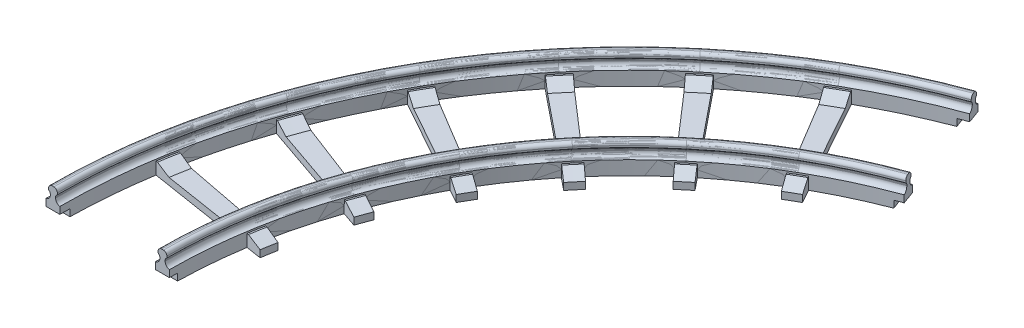
SolidWorks part; units mm, degrees
other "标注1"
sketch "草图3" plane through (-22.25, 4, -10) normal (-0.231, 0.6469, -0.7268) x (-0.9696, -0.2151, 0.1167)
ref_plane "前视基准面" through (0, 0, 0) normal (0, 0, 1) x (1, 0, 0)
ref_plane "上视基准面" through (0, 0, 0) normal (0, 1, 0) x (1, 0, 0)
ref_plane "右视基准面" through (0, 0, 0) normal (1, 0, 0) x (0, 0, -1)
other "Configuration Table"
sketch "草图4" plane through (0, 0, 0) normal (0, 0, 1) x (1, 0, 0)
  line L0 (0, 0) -> (31.5, 0) construction
  line L1 (0.75, -1.5) -> (1.25, -1.5)
  line L3 (0, 0) -> (1.25, 0)
  line L4 (1.25, -1.5) -> (1.25, 0)
  line L5 (0, 0) -> (-1.25, 0)
  line L10 (0.75, -1.5) -> (0.75, -4)
  line L11 (-0.75, -1.5) -> (-1.25, -1.5)
  line L12 (0.75, -4) -> (2, -4)
  line L14 (0, -8) -> (2, -8)
  line L15 (2, -4) -> (2, -8)
  line L16 (-1.25, 0) -> (-1.25, -1.5)
  line L20 (-0.75, -1.5) -> (-0.75, -4)
  line L21 (-0.75, -4) -> (-2, -4)
  line L23 (0, -8) -> (-2, -8)
  line L24 (-2, -4) -> (-2, -8)
  line L25 (31.5, 0) -> (32.75, 0)
  line L26 (30.25, 0) -> (31.5, 0)
  line L27 (30.25, 0) -> (30.25, -1.5)
  line L28 (30.25, -1.5) -> (30.75, -1.5)
  line L31 (30.75, -1.5) -> (30.75, -4)
  line L34 (29.5, -4) -> (30.75, -4)
  line L35 (29.5, -4) -> (29.5, -8)
  line L36 (29.5, -8) -> (31.5, -8)
  line L39 (32.25, -1.5) -> (32.75, -1.5)
  line L40 (32.75, 0) -> (32.75, -1.5)
  line L42 (32.25, -1.5) -> (32.25, -4)
  line L45 (32.25, -4) -> (33.5, -4)
  line L47 (31.5, -8) -> (33.5, -8)
  line L48 (33.5, -4) -> (33.5, -8)
  point P0 (0, 0)
  point P2 (15.75, 0)
  dimension "D1" = 1.25
  dimension "D4" = 2.5
sketch "草图6" plane through (0, 0, 0) normal (0, 0, 1) x (1, 0, 0)
  line L0 (165.75, 3.8535) -> (165.75, -12.2756)
  dimension "D1" = 150
revolve "旋转1" add sketch "草图4" angle 10 about L0
fillet "圆角1" radius 1.5 2 edges at (1.3779, -4, -14.3807) (-0.1164, -4, -14.5114)
fillet "圆角2" radius 1.5 2 edges at (31.2637, -4, -11.766) (32.758, -4, -11.6353)
fillet "圆角3" radius 1 4 edges at (33.2561, 0, -11.5917) (30.7656, 0, -11.8096) (31.2637, -1.5, -11.766) (32.758, -1.5, -11.6353)
fillet "圆角4" radius 1 4 edges at (1.876, 0, -14.3371) (-0.1164, -1.5, -14.5114) (1.3779, -1.5, -14.3807) (-0.6145, 0, -14.555)
sketch "草图7" plane through (0, 0, 0) normal (0, 0, 1) x (1, 0, 0)
  line L1 (-2, -8) -> (2, -8)
  line L2 (-2, -8) -> (-2, -6)
  line L3 (-2, -6) -> (2, -6)
  line L4 (2, -8) -> (2, -6)
  line L5 (33.5, -8) -> (33.5, -4) construction
  line L6 (29.5, -8) -> (33.5, -8)
  line L7 (29.5, -8) -> (29.5, -6)
  line L8 (29.5, -6) -> (33.5, -6)
  line L9 (33.5, -8) -> (33.5, -6)
  line L10 (2, -8) -> (2, -4) construction
  dimension "D1" = 2
sketch "草图9" plane through (0, 0, 0) normal (0, 1, 0) x (1, 0, 0)
  line L0 (29.5, 0) -> (2, 0)
  line L1 (-2, 0) -> (2, 0) construction
  line L2 (4.4877, 28.4349) -> (31.5699, 23.6596)
  line L3 (18.0288, 26.0472) -> (15.75, 0)
  arc A0 (4.4877, 28.4349) -> (2, 0) centre (165.75, 0) ccw construction
  arc A1 (31.5699, 23.6596) -> (29.5, 0) centre (165.75, 0) ccw construction
  point P20 (165.75, 0)
  dimension "D1" = 10
  dimension "D2" = 26.1467
revolve "切除-旋转1" cut sketch "草图7" angle 1 about L0
sketch "草图10" plane through (0, -6, 0) normal (0, -1, 0) x (1, 0, 0)
  line L0 (-1.9936, -1.4639) -> (2.0062, -1.429) construction
  line L2 (2.0062, -1.429) -> (29.5052, -1.189) construction
  line L3 (29.5052, -1.189) -> (33.505, -1.1541) construction
  circle A1 centre (0.0063, -1.4464) radius 0.4
  circle A2 centre (31.5051, -1.1715) radius 0.4
  arc A3 (-2, 0) -> (-1.9745, -2.9276) centre (165.75, 0) ccw construction
  arc A4 (2, 0) -> (2.0249, -2.8578) centre (165.75, 0) ccw construction
  arc A5 (29.5, 0) -> (29.5208, -2.3779) centre (165.75, 0) ccw construction
  arc A6 (33.5, 0) -> (33.5201, -2.3081) centre (165.75, 0) ccw construction
  dimension "D1" = 0.8
extrude "切除-拉伸1" cut sketch "草图10" against normal blind 2
sketch "草图11" plane through (4.998, 0, -28.3449) normal (0.1736, 0, -0.9848) x (-0.9848, 0, -0.1736)
  line L0 (-26.9819, -4.5) -> (-26.4819, -4.5)
  line L1 (-26.9819, -4) -> (-26.9819, -8) construction
  line L2 (-26.4819, -4.5) -> (-22.4819, -6)
  line L3 (-22.4819, -6) -> (-3.9819, -6)
  line L4 (-3.9819, -6) -> (0.0181, -4.5)
  line L5 (0.0181, -4.5) -> (0.5181, -4.5)
  line L6 (0.5181, -8) -> (0.5181, -4) construction
  line L7 (0.5181, -4.5) -> (4.5181, -4.5)
  line L8 (4.5181, -4) -> (4.5181, -8) construction
  line L9 (4.5181, -4.5) -> (5.0181, -4.5)
  line L10 (5.0181, -4.5) -> (9.0181, -6)
  line L11 (9.0181, -6) -> (9.0181, -8)
  line L13 (-35.4819, -8) -> (-35.4819, -6)
  line L14 (-35.4819, -6) -> (-31.4819, -4.5)
  line L15 (-31.4819, -4.5) -> (-30.9819, -4.5)
  line L16 (-30.9819, -8) -> (-30.9819, -4) construction
  line L17 (-30.9819, -4.5) -> (-26.9819, -4.5)
  line L19 (-35.4819, -8) -> (-30.9819, -8)
  line L20 (-30.9819, -8) -> (-26.9819, -8)
  line L21 (-26.9819, -8) -> (0.5181, -8)
  line L22 (0.5181, -8) -> (4.5181, -8)
  line L23 (4.5181, -8) -> (9.0181, -8)
  dimension "D1" = 0.5
  dimension "D2" = 4.5
  dimension "D3" = 3.5
  dimension "D4" = 2
revolve "旋转2" add sketch "草图11" angle 1 about L0
mirror "镜向1"
pattern_circular "阵列(圆周)1" count 6 every 10 about axis through (165.75, 0, 0) along (0, 1, 0) of bodies 229
